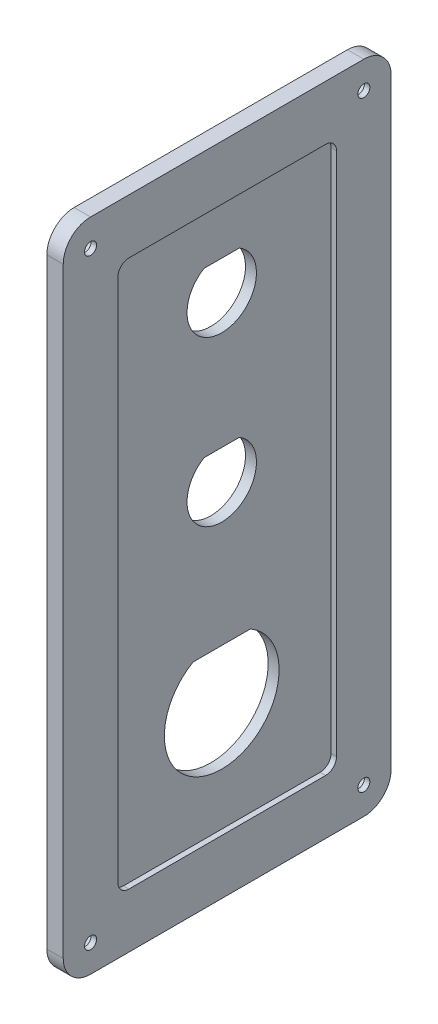
SolidWorks part; units mm, degrees
material "6061 Alloy"
ref_plane "Front Plane" through (0, 0, 0) normal (0, 0, 1) x (1, 0, 0)
ref_plane "Top Plane" through (0, 0, 0) normal (0, 1, 0) x (1, 0, 0)
ref_plane "Right Plane" through (0, 0, 0) normal (1, 0, 0) x (0, 0, -1)
sketch "Sketch1" plane through (0, 0, 0) normal (1, 0, 0) x (0, 0, -1)
  line L1 (-30, 60) -> (30, 60)
  line L2 (-30, 60) -> (-30, -60)
  line L3 (-30, -60) -> (30, -60)
  line L4 (30, 60) -> (30, -60)
  line L5 (-20, 50) -> (20, 50)
  line L6 (-20, 50) -> (-20, -50)
  line L7 (-20, -50) -> (20, -50)
  line L8 (20, 50) -> (20, -50)
  dimension "D1" = 120
  dimension "D2" = 60
  dimension "D3" = 30
  dimension "D4" = 60
  dimension "D5" = 40
  dimension "D6" = 100
  dimension "D7" = 50
  dimension "D8" = 20
extrude "Boss-Extrude1" add sketch "Sketch1" along normal blind 3
extrude "Boss-Extrude2" add sketch "Sketch1<3>" along normal blind 2 contours L8 L7 L6 L5
sketch "Sketch1<3>" plane through (0, 0, 0) normal (1, 0, 0) x (0, 0, -1) same geometry as "Sketch1"
sketch "Sketch2" plane through (0, 0, 0) normal (-1, 0, 0) x (0, 0, 1)
  line L0 (-30, -60) -> (-30, 60) construction
  line L1 (-30, 60) -> (30, 60) construction
  line L2 (30, 60) -> (30, -60) construction
  line L3 (30, -60) -> (-30, -60) construction
  circle A0 centre (-25, 55) radius 2
  circle A1 centre (25, 55) radius 2
  circle A2 centre (-25, -55) radius 2
  circle A3 centre (25, -55) radius 2
  dimension "D3" = 4
  dimension "D4" = 5
  dimension "D5" = 5
  dimension "D1" = 5
  dimension "D2" = 5
extrude "Cut-Extrude1" cut sketch "Sketch2" against normal blind 2
sketch "Sketch3" plane through (0, 0, 0) normal (-1, 0, 0) x (0, 0, 1)
  circle A0 centre (-25, 55) radius 1.1
  circle A1 centre (25, 55) radius 1.1
  circle A2 centre (-25, -55) radius 1.1
  circle A3 centre (25, -55) radius 1.1
  dimension "D1" = 2.2
extrude "Cut-Extrude2" cut sketch "Sketch3" against normal blind 3
fillet "Fillet1" radius 5 4 edges at (1.5, -60, 30) (1.5, -60, -30) (1.5, 60, -30) (1.5, 60, 30)
fillet "Fillet2" radius 2 4 edges at (2.5, 50, 20) (2.5, -50, 20) (2.5, -50, -20) (2.5, 50, -20)
sketch "Sketch4" plane through (2, 0, 0) normal (1, 0, 0) x (0, 0, -1)
  line L0 (-18, 50) -> (18, 50) construction
  line L1 (-18, -50) -> (18, -50) construction
  line L2 (-3.225, 40.4701) -> (3.225, 40.4701)
  line L3 (-3.225, 10.4701) -> (3.225, 10.4701)
  line L4 (-5.24, -20.901) -> (5.24, -20.901)
  arc A0 (-3.225, 40.4701) -> (3.225, 40.4701) centre (0, 35) ccw
  arc A1 (-3.225, 10.4701) -> (3.225, 10.4701) centre (0, 5) ccw
  arc A2 (-5.24, -20.901) -> (5.24, -20.901) centre (0, -30) ccw
  dimension "D1" = 12.7
  dimension "D4" = 21
  dimension "D2" = 15
  dimension "D3" = 20
  dimension "D5" = 30
  dimension "D6" = 6.45
  dimension "D7" = 6.45
  dimension "D8" = 10.48
extrude "Cut-Extrude3" cut sketch "Sketch4" against normal blind 2
sketch "Sketch5" plane through (0, 0, 0) normal (-1, 0, 0) x (0, 0, 1)
  line L0 (0, 49.8237) -> (0, -51.0972) construction
  line L1 (-2.5, 20.4701) -> (2.5, 20.4701) construction
  line L2 (-9, -9.5299) -> (9, -9.5299) construction
  line L3 (-2.5, -50.901) -> (2.5, -50.901) construction
  line L4 (-3.225, 40.4701) -> (3.225, 40.4701) construction
  line L5 (-3.225, 10.4701) -> (3.225, 10.4701) construction
  line L6 (-5.24, -20.901) -> (5.24, -20.901) construction
  text T0 "<b>J1</b>" font "Times New Roman" height 3.5
  text T1 "<b>J1/CCD</b>" font "Times New Roman" height 3.5
  text T2 "<b>J2</b>" font "Times New Roman" height 3.5
  point P5 (0, 20.4701)
  point P8 (0, -9.5299)
  point P11 (0, -50.901)
  point P12 (0, 0)
  point P20 (-3.6241, 20.4701)
  point P21 (-2.1578, 20.4701)
  point P22 (0, 0)
  point P23 (0, 0)
  point P24 (-3.3308, 20.4701)
  point P25 (2.0317, 20.4701)
  point P26 (0, 0)
  point P27 (10.5062, -9.5299)
  point P28 (8.2528, -9.5299)
  point P29 (0, 0)
  point P30 (0, 0)
  point P31 (10.0055, -9.5299)
  point P33 (2.5, -50.901)
  dimension "D1" = 20
  dimension "D2" = 20
  dimension "D3" = 30
  dimension "D4" = 5
  dimension "D5" = 18
  dimension "D6" = 5
extrude "Boss-Extrude3" add sketch "Sketch5" along normal blind 0.5
